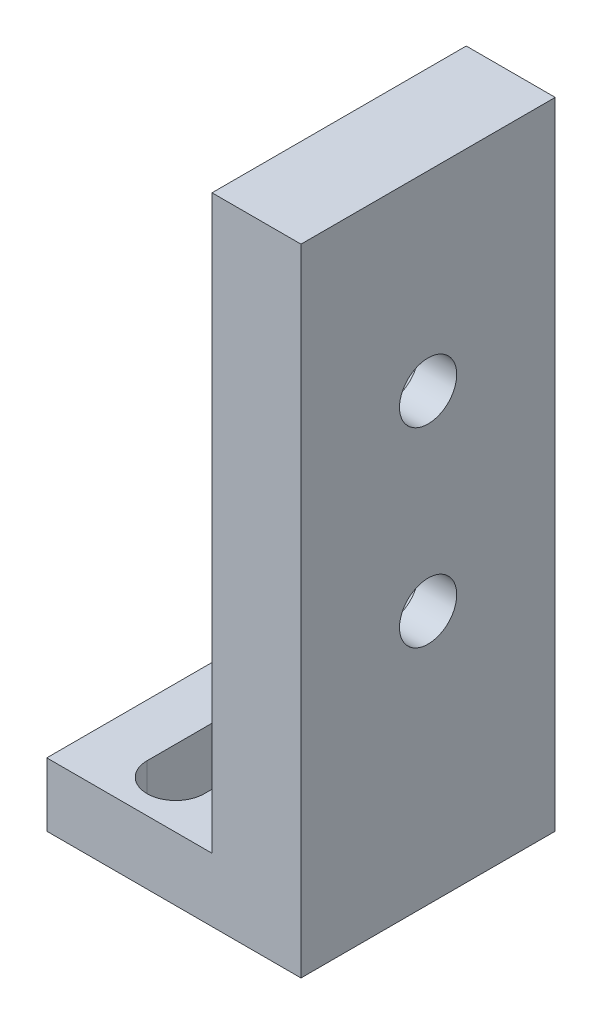
SolidWorks part; units mm, degrees
ref_plane "Plano frontal" through (0, 0, 0) normal (0, 0, 1) x (1, 0, 0)
ref_plane "Plano superior" through (0, 0, 0) normal (0, 1, 0) x (1, 0, 0)
ref_plane "Plano direito" through (0, 0, 0) normal (1, 0, 0) x (0, 0, -1)
sketch "Esboço1" plane through (0, 0, 0) normal (0, 0, 1) x (1, 0, 0)
  line L0 (0, 0) -> (0, 5)
  line L1 (0, 5) -> (13, 5)
  line L2 (13, 5) -> (13, 50)
  line L3 (13, 50) -> (20, 50)
  line L4 (20, 50) -> (20, 0)
  line L5 (20, 0) -> (0, 0)
  dimension "D1" = 20
  dimension "D2" = 50
  dimension "D3" = 7
  dimension "D4" = 5
extrude "Ressalto-extrusão1" add sketch "Esboço1" along normal blind 20
sketch "Esboço2" plane through (0, 5, 0) normal (0, 1, 0) x (1, 0, 0)
  line L0 (6.39, -3.75) -> (6.39, -16.25) construction
  line L1 (8.64, -3.75) -> (8.64, -16.25)
  line L2 (4.14, -3.75) -> (4.14, -16.25)
  line L3 (0, -20) -> (0, 0) construction
  line L4 (13, -20) -> (0, -20) construction
  arc A0 (8.64, -3.75) -> (4.14, -3.75) centre (6.39, -3.75) ccw
  arc A1 (4.14, -16.25) -> (8.64, -16.25) centre (6.39, -16.25) ccw
  point P2 (6.39, -10)
  dimension "D4" = 12.5
  dimension "D2" = 2.25
  dimension "D1" = 6.39
  dimension "D3" = 10
extrude "Corte-extrusão1" cut sketch "Esboço2" against normal through all
sketch "Esboço3" plane through (13, 0, 0) normal (-1, 0, 0) x (0, 0, 1)
  line L0 (20, 50) -> (20, 5) construction
  line L1 (20, 50) -> (0, 50) construction
  line L2 (10, 23.5) -> (10, 31.5) construction
  line L3 (5.9585, 20) -> (7.9793, 16.5)
  line L4 (7.9793, 16.5) -> (12.0207, 16.5)
  line L5 (12.0207, 16.5) -> (14.0415, 20)
  line L6 (14.0415, 20) -> (12.0207, 23.5)
  line L7 (12.0207, 23.5) -> (7.9793, 23.5)
  line L8 (7.9793, 23.5) -> (5.9585, 20)
  line L9 (5.9585, 35) -> (7.9793, 31.5)
  line L10 (7.9793, 31.5) -> (12.0207, 31.5)
  line L11 (12.0207, 31.5) -> (14.0415, 35)
  line L12 (14.0415, 35) -> (12.0207, 38.5)
  line L13 (12.0207, 38.5) -> (7.9793, 38.5)
  line L14 (7.9793, 38.5) -> (5.9585, 35)
  line L15 (20, 27.5) -> (0, 27.5) construction
  line L16 (0, 50) -> (0, 5) construction
  circle A0 centre (10, 35) radius 2.25
  circle A1 centre (10, 20) radius 2.25
  circle A2 centre (10, 20) radius 3.5 construction
  circle A3 centre (10, 35) radius 3.5 construction
  point P8 (6.75, 34.4236)
  point P29 (10, 27.5)
  point P30 (20, 29)
  dimension "D3" = 4.5
  dimension "D5" = 7
  dimension "D1" = 15
  dimension "D2" = 10
  dimension "D4" = 15
extrude "Corte-extrusão2" cut sketch "Esboço3" against normal through all contours A0 | A1 region at (13, 35, 10) region at (13, 20, 10)
extrude "Cut-Extrude1" cut sketch "Esboço3<3>" against normal blind 4
sketch "Esboço3<3>" plane through (13, 0, 0) normal (-1, 0, 0) x (0, 0, 1) same geometry as "Esboço3"
